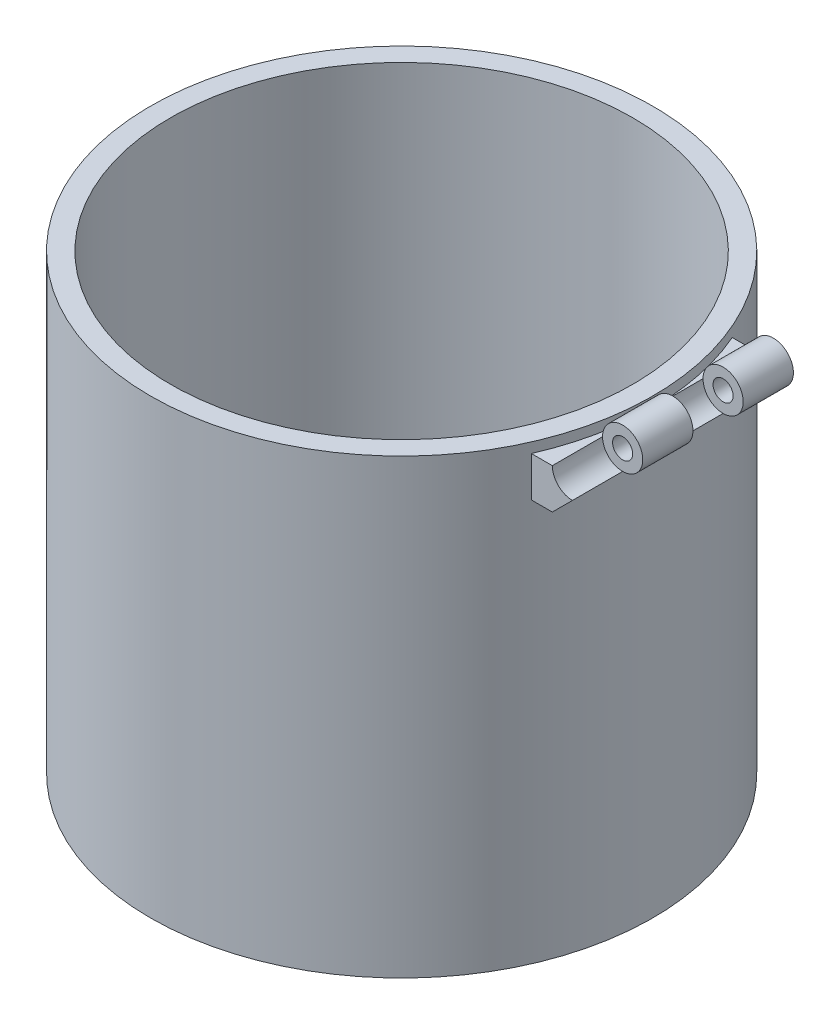
SolidWorks part; units mm, degrees
ref_plane "Front Plane" through (0, 0, 0) normal (0, 0, 1) x (1, 0, 0)
ref_plane "Top Plane" through (0, 0, 0) normal (0, 1, 0) x (1, 0, 0)
ref_plane "Right Plane" through (0, 0, 0) normal (1, 0, 0) x (0, 0, -1)
sketch "Sketch1" plane through (0, 0, 0) normal (0, 1, 0) x (1, 0, 0)
  circle A0 centre (0, 0) radius 25
  dimension "D1" = 50
extrude "Boss-Extrude1" add sketch "Sketch1" along normal blind 45
shell "Shell1" thickness 2 removed face at (0, 45, 25)
sketch "Sketch2" plane through (0, 2, 0) normal (0, 1, 0) x (1, 0, 0)
  line L0 (0, 0) -> (13.888, 0) construction
  line L1 (0, 0) -> (9.7749, 16.9307) construction
  circle A1 centre (15, 0) radius 3.5
  circle A2 centre (7.5, -12.9904) radius 3.5
  circle A3 centre (-7.5, -12.9904) radius 3.5
  circle A4 centre (-15, 0) radius 3.5
  circle A5 centre (-7.5, 12.9904) radius 3.5
  circle A6 centre (7.5, 12.9904) radius 3.5
  point P2 (7.4998, 12.99)
  point P18 (0, 0)
  dimension "D1" = 7
  dimension "D2" = 15
  dimension "D4" = 60
  dimension "D5" = 15
  dimension "D3" = 6
extrude "Cut-Extrude1" cut sketch "Sketch2" against normal up to surface (2 mm away) up to face at (0, 0, 25)
sketch "Sketch3" plane through (0, 0, 0) normal (0, 0, 1) x (1, 0, 0)
  line L4 (25, 44) -> (25, 40)
  line L5 (25, 0) -> (25, 45) construction
  line L6 (25, 40) -> (27, 42)
  line L7 (25, 45) -> (-25, 45) construction
  arc A2 (27, 42) -> (25, 44) centre (27, 44) ccw
  point P1 (27.7304, 44.8604)
  point P9 (0, 0)
  point P10 (27.5218, 45.762)
  point P11 (0, 0)
  point P13 (27.3802, 44.458)
  point P14 (25.9408, 41.9408)
  point P15 (27, 41.9714)
  point P16 (26.6478, 41.6478)
  point P18 (27.6364, 43.6679)
  dimension "D1" = 4
  dimension "D2" = 1
  dimension "D4" = 4
  dimension "D3" = 45
extrude "Boss-Extrude4" add sketch "Sketch3" along normal blind 10 and the other way blind 10 separate body
sketch "Sketch8" plane through (25, 0, 0) normal (-1, 0, 0) x (0, 0, 1)
  line L1 (10, 40) -> (-10, 40)
  line L2 (10, 40) -> (10, 44)
  line L3 (10, 44) -> (-10, 44)
  line L4 (-10, 40) -> (-10, 44)
extrude "Boss-Extrude6" add sketch "Sketch8" along normal up to surface up to face at (0, 45, 25)
sketch "Sketch9" plane through (0, 0, 10) normal (0, 0, 1) x (1, 0, 0)
  circle A0 centre (27, 44) radius 1
  dimension "D1" = 2
extrude "Cut-Extrude4" cut sketch "Sketch9" against normal through all both and the other way through all
sketch "Sketch10" plane through (0, 0, 10) normal (0, 0, 1) x (1, 0, 0)
  circle A0 centre (27, 44) radius 2
extrude "Cut-Extrude5" cut sketch "Sketch10" against normal blind 5
pattern_linear "LPattern2" count 2 spacing 10 along (0, 0, -1) of "Cut-Extrude5"
